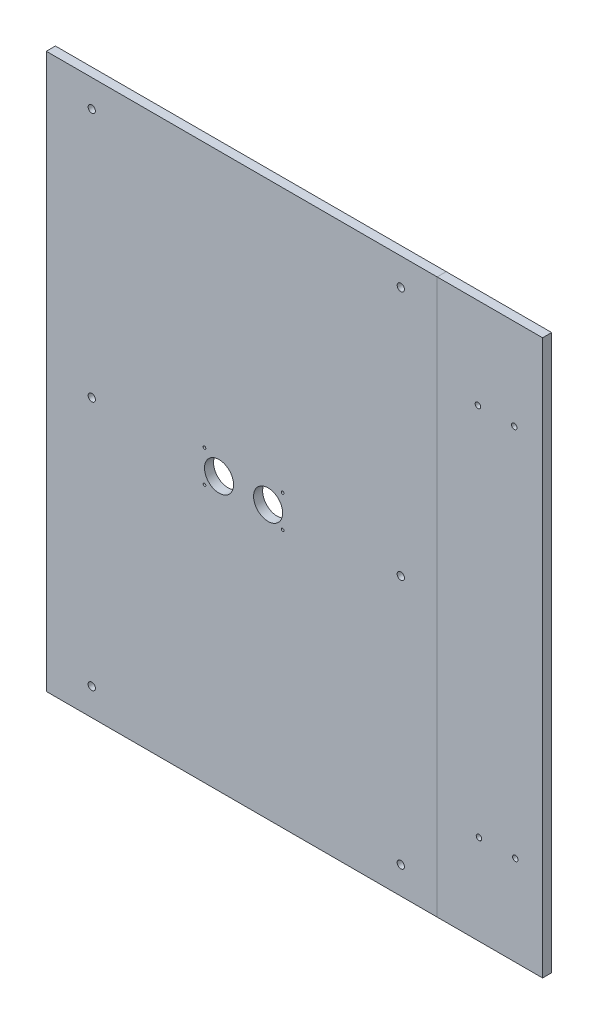
SolidWorks part; units mm, degrees
ref_plane "Plan de face" through (0, 0, 0) normal (0, 0, 1) x (1, 0, 0)
ref_plane "Plan de dessus" through (0, 0, 0) normal (0, 1, 0) x (1, 0, 0)
ref_plane "Plan de droite" through (0, 0, 0) normal (1, 0, 0) x (0, 0, -1)
sketch "Esquisse1" plane through (0, 0, 0) normal (0, 0, 1) x (1, 0, 0)
  line L1 (0, 0) -> (215, 0)
  line L2 (0, 0) -> (0, 305)
  line L3 (0, 305) -> (215, 305)
  line L4 (215, 0) -> (215, 305)
  dimension "D1" = 305
  dimension "D2" = 215
extrude "Boss.-Extru.1" add sketch "Esquisse1" along normal blind 5
sketch "Esquisse2" plane through (0, 0, 0) normal (0, 0, -1) x (-1, 0, 0)
  line L0 (-215, 0) -> (-215, 305) construction
  line L1 (-215, 305) -> (0, 305) construction
  line L2 (0, 305) -> (0, 0) construction
  line L3 (0, 0) -> (-215, 0) construction
  circle A0 centre (-195, 290) radius 2
  circle A1 centre (-25, 290) radius 2
  circle A2 centre (-25, 15) radius 2
  circle A3 centre (-195, 15) radius 2
  circle A4 centre (-195, 152.5) radius 2
  circle A5 centre (-25, 152.5) radius 2
  dimension "D1" = 4
  dimension "D2" = 4
  dimension "D3" = 4
  dimension "D4" = 4
  dimension "D5" = 20
  dimension "D6" = 20
  dimension "D8" = 15
  dimension "D9" = 25
  dimension "D10" = 15
  dimension "D11" = 25
  dimension "D12" = 15
  dimension "D13" = 4
  dimension "D14" = 4
  dimension "D15" = 152.5
  dimension "D16" = 152.5
  dimension "D17" = 20
  dimension "D18" = 25
  dimension "D7" = 15
extrude "Enlèv. mat.-Extru.1" cut sketch "Esquisse2" against normal blind 5
sketch "Esquisse3" plane through (0, 0, 0) normal (0, 0, -1) x (-1, 0, 0)
  line L1 (-215, 305) -> (-273, 305)
  line L2 (-215, 305) -> (-215, 0)
  line L3 (-215, 0) -> (-273, 0)
  line L4 (-273, 305) -> (-273, 0)
  dimension "D1" = 58
extrude "Boss.-Extru.2" add sketch "Esquisse3" against normal blind 5 separate body
sketch "Esquisse4" plane through (0, 0, 0) normal (0, 0, -1) x (-1, 0, 0)
  circle A0 centre (-237.4, 255) radius 1.5
  circle A1 centre (-257.4, 255) radius 1.5
  dimension "D1" = 3
  dimension "D2" = 3
extrude "Enlèv. mat.-Extru.3" cut sketch "Esquisse4" against normal through all
sketch "Esquisse5" plane through (0, 0, 5) normal (0, 0, 1) x (1, 0, 0)
  circle A0 centre (238, 49.5) radius 1.5
  circle A1 centre (258, 49.5) radius 1.5
  dimension "D1" = 3
  dimension "D2" = 3
extrude "Enlèv. mat.-Extru.4" cut sketch "Esquisse5" against normal through all
sketch "Esquisse6" plane through (0, 0, 0) normal (0, 0, -1) x (-1, 0, 0)
  line L0 (0, 305) -> (0, 0) construction
  line L1 (0, 0) -> (-215, 0) construction
  circle A0 centre (-122, 150) radius 8
  circle A1 centre (-95, 150) radius 8
  dimension "D1" = 16
  dimension "D2" = 16
  dimension "D3" = 27
  dimension "D4" = 95
  dimension "D5" = 150
  dimension "D6" = 150
extrude "Enlèv. mat.-Extru.5" cut sketch "Esquisse6" against normal through all
sketch "Esquisse7" plane through (0, 0, 0) normal (0, 0, -1) x (-1, 0, 0)
  line L0 (-86, 161) -> (-131, 161) construction
  line L1 (-131, 161) -> (-131, 141) construction
  line L2 (-131, 141) -> (-70.8007, 141) construction
  line L3 (-86, 161) -> (-86, 141) construction
  line L4 (0, 0) -> (-215, 0) construction
  line L5 (-215, 305) -> (0, 305) construction
  circle A0 centre (-87, 159.7) radius 0.75
  circle A1 centre (-130, 159.7) radius 0.75
  circle A2 centre (-87, 142) radius 0.75
  circle A3 centre (-130, 142) radius 0.75
  circle A4 centre (-95, 150) radius 8 construction
  dimension "D1" = 1.5
  dimension "D2" = 1.5
  dimension "D3" = 1.5
  dimension "D4" = 1.5
  dimension "D5" = 20
  dimension "D6" = 45
  dimension "D7" = 11
  dimension "D8" = 1
  dimension "D9" = 1.3
  dimension "D10" = 1
  dimension "D11" = 9
  dimension "D12" = 1
  dimension "D13" = 1
  dimension "D14" = 1
  dimension "D15" = 1
  dimension "D16" = 1.3
extrude "Enlèv. mat.-Extru.7" cut sketch "Esquisse7" against normal through all
